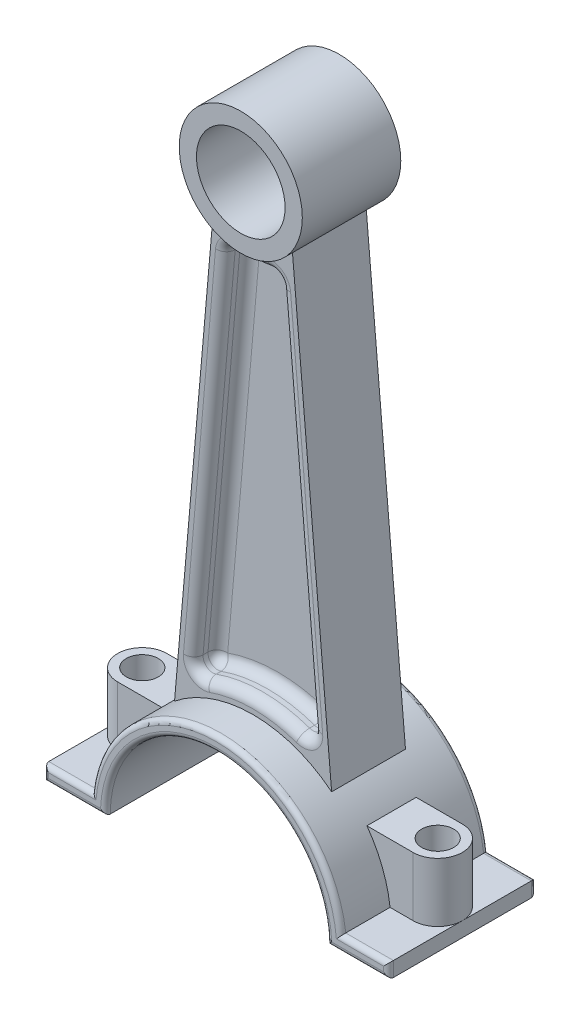
SolidWorks part; units mm, degrees
material "Cast Carbon Steel"
ref_plane "Front Plane" through (0, 0, 0) normal (0, 0, 1) x (1, 0, 0)
ref_plane "Top Plane" through (0, 0, 0) normal (0, 1, 0) x (1, 0, 0)
ref_plane "Right Plane" through (0, 0, 0) normal (1, 0, 0) x (0, 0, -1)
sketch "Sketch1" plane through (0, 0, 0) normal (0, 0, 1) x (1, 0, 0)
  line L0 (0, 0) -> (0, -120.4) construction
  line L1 (-35, -120.4) -> (-22.5, -120.4)
  line L2 (22.5, -120.4) -> (35, -120.4)
  line L3 (-35, -117.4) -> (-25.3229, -117.4)
  line L4 (25.3229, -117.4) -> (35, -117.4)
  line L5 (-35, -120.4) -> (-35, -117.4)
  line L6 (35, -120.4) -> (35, -117.4)
  line L7 (-8, -9.6047) -> (-15.9529, -100.5064)
  line L8 (8, -9.6047) -> (15.9529, -100.5064)
  circle A0 centre (0, 0) radius 9
  circle A1 centre (0, 0) radius 12.5
  arc A2 (22.5, -120.4) -> (-22.5, -120.4) centre (0, -120.4) ccw
  arc A3 (25.3229, -117.4) -> (-25.3229, -117.4) centre (0, -120.4) ccw
  dimension "D1" = 25
  dimension "D2" = 18
  dimension "D4" = 45
  dimension "D3" = 120.4
  dimension "D5" = 70
  dimension "D6" = 3
  dimension "D7" = 8
  dimension "D8" = 5
extrude "Boss-Extrude1" add sketch "Sketch1" along normal mid plane 20 contours A0 A1 region at (-5.1533, 10.9991, 0)
extrude "Boss-Extrude2" add sketch "Sketch1<4>" along normal mid plane 30 separate body contours A3 L0 A2 L2 L6 L4 | L0 A3 L3 L5 L1 A2 region at (8.3111, -96.7509, 0) region at (-0.433, -96.4, 0)
sketch "Sketch1<4>" plane through (0, 0, 0) normal (0, 0, 1) x (1, 0, 0) same geometry as "Sketch1"
extrude "Boss-Extrude3" add sketch "Sketch1<5>" along normal mid plane 15 contours L0 A1 L7 A3 | A1 L0 A3 L8 region at (6.2653, -58.5545, 0) region at (-6.2653, -58.5545, 0)
sketch "Sketch1<5>" plane through (0, 0, 0) normal (0, 0, 1) x (1, 0, 0) same geometry as "Sketch1"
sketch "Sketch2" plane through (0, 0, 0) normal (0, 0, 1) x (1, 0, 0)
  line L8 (12.4385, -94.7576) -> (5.4187, -14.522)
  line L9 (-5.4187, -14.522) -> (-12.4385, -94.7576)
  line L10 (12.4385, -94.7576) -> (5.4187, -14.522)
  line L11 (-5.4187, -14.522) -> (-12.4385, -94.7576)
  arc A8 (12.4385, -94.7576) -> (-12.4385, -94.7576) centre (0, -120.4) ccw
  arc A9 (-5.4187, -14.522) -> (5.4187, -14.522) centre (0, 0) ccw
  arc A10 (12.4385, -94.7576) -> (-12.4385, -94.7576) centre (0, -120.4) ccw
  arc A11 (-5.4187, -14.522) -> (5.4187, -14.522) centre (0, 0) ccw
  dimension "D2" = 3
extrude "Cut-Extrude1" cut sketch "Sketch2" against normal blind 5 and the other way through all from offset 7.5
mirror "Mirror1" about plane through (0, 0, 0) normal (0, 0, 1) of "Cut-Extrude1"
sketch "Sketch3" plane through (0, -117.4, 0) normal (0, 1, 0) x (1, 0, 0)
  line L0 (35, -15) -> (35, 15) construction
  line L1 (18, 5) -> (30, 5)
  line L2 (18, 5) -> (18, -5)
  line L3 (18, -5) -> (30, -5)
  line L4 (30, 5) -> (30, -5)
  line L5 (18, 5) -> (30, -5) construction
  line L6 (18, -5) -> (30, 5) construction
  circle A0 centre (30, 0) radius 5
  circle A1 centre (30, 0) radius 3.25
  point P0 (24, 0)
  line M8 (25.3229, 15) -> (25.3229, -15)
  dimension "D1" = 10
  dimension "D3" = 6.5
  dimension "D2" = 12
extrude "Boss-Extrude4" add sketch "Sketch3" against normal up to body from offset 12 contours A0 L1 L2 L3 M8 | A0 L1 M8 | L4 A1 | L4 A1 | A1 L4 A0 M8 | A0 L3 M8 | A1 L4 A0 | A0 M8 region at (21.6241, -117.4, 0) region at (26.4044, -117.4, -4.1253) region at (33.4565, -117.4, -3.4565) region at (29.8896, -117.4, -4.125) region at (25.1934, -117.4, 0) region at (26.4044, -117.4, 4.1253) region at (31.3793, -117.4, 0) region at (28.6207, -117.4, 0)
extrude "Cut-Extrude2" cut sketch "Sketch3<3>" against normal through all from surface contours L4 A1 | L4 A1 region at (31.3793, -117.4, 0) region at (28.6207, -117.4, 0) starting at face at (26.5608, -105.4, 0)
sketch "Sketch3<3>" plane through (0, -117.4, 0) normal (0, 1, 0) x (1, 0, 0) same geometry as "Sketch3"
mirror "Mirror2" about plane through (0, 0, 0) normal (1, 0, 0) of "Boss-Extrude4", "Cut-Extrude2"
fillet "Fillet1" radius 2 24 edges at (8.9286, -54.6398, -2.5) (0, -15.5, -2.5) (-8.9286, -54.6398, -2.5) (0, -91.9, -2.5) (-8.9286, -54.6398, 2.5) (0, -15.5, 2.5) (8.9286, -54.6398, 2.5) (0, -91.9, 2.5) (-12.4385, -94.7576, 5) (8.9286, -54.6398, 7.5) (0, -91.9, 7.5) (0, -15.5, 7.5) (-8.9286, -54.6398, -7.5) (8.9286, -54.6398, -7.5) (-8.9286, -54.6398, 7.5) (5.4187, -14.522, 5) (-5.4187, -14.522, 5) (12.4385, -94.7576, 5) (0, -91.9, -7.5) (-12.4385, -94.7576, -5) (12.4385, -94.7576, -5) (-5.4187, -14.522, -5) (5.4187, -14.522, -5) (0, -15.5, -7.5)
fillet "Fillet2" radius 1 16 edges at (30.1615, -117.4, 15) (35, -118.9, 15) (28.75, -120.4, 15) (0, -97.9, 15) (-28.75, -120.4, 15) (-35, -118.9, 15) (-30.1615, -117.4, 15) (0, -94.9, 15) (-30.1615, -117.4, -15) (-35, -118.9, -15) (-28.75, -120.4, -15) (0, -97.9, -15) (28.75, -120.4, -15) (35, -118.9, -15) (30.1615, -117.4, -15) (0, -94.9, -15)
